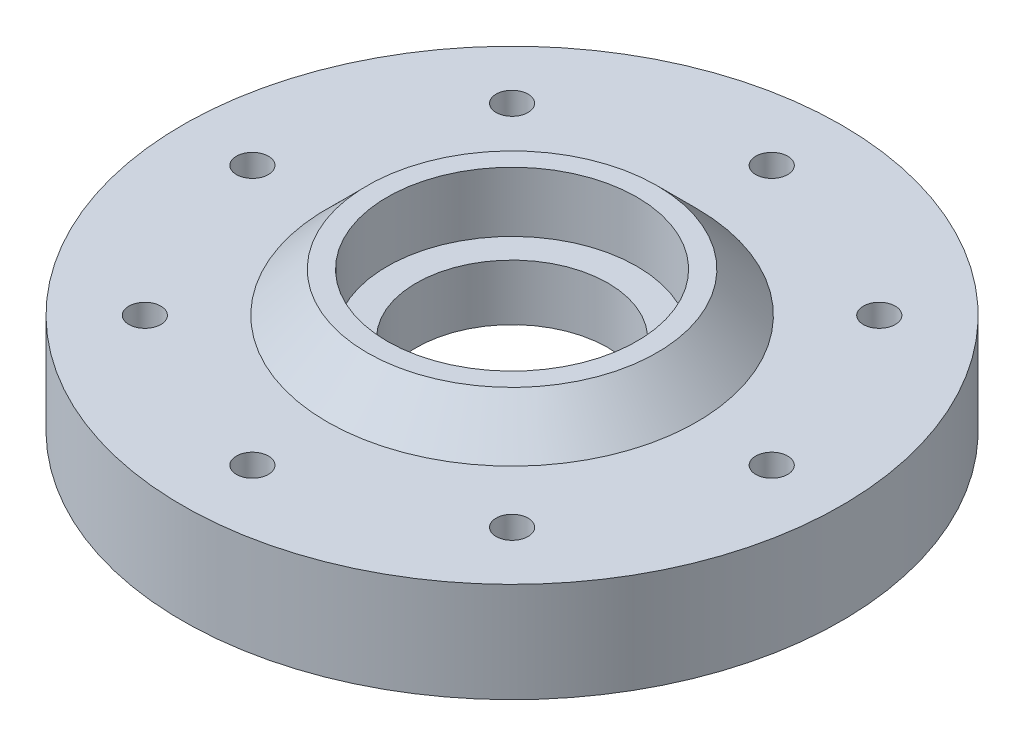
SolidWorks part; units mm, degrees
material "Plain Carbon Steel"
ref_plane "Front Plane" through (0, 0, 0) normal (0, 0, 1) x (1, 0, 0)
ref_plane "Top Plane" through (0, 0, 0) normal (0, 1, 0) x (1, 0, 0)
ref_plane "Right Plane" through (0, 0, 0) normal (1, 0, 0) x (0, 0, -1)
sketch "Sketch1" plane through (0, 0, 0) normal (0, 1, 0) x (1, 0, 0)
  circle A0 centre (0, 0) radius 56 construction
  circle A1 centre (0, 0) radius 82.5 construction
  circle A2 centre (65, 0) radius 4 construction
  circle A3 centre (65, 0) radius 4
  circle A4 centre (45.9619, -45.9619) radius 4 construction
  circle A5 centre (0, -65) radius 4 construction
  circle A6 centre (-45.9619, -45.9619) radius 4 construction
  circle A7 centre (-65, 0) radius 4 construction
  circle A8 centre (-45.9619, 45.9619) radius 4 construction
  circle A9 centre (0, 65) radius 4 construction
  circle A10 centre (45.9619, 45.9619) radius 4 construction
  circle A11 centre (45.9619, -45.9619) radius 4
  circle A12 centre (0, -65) radius 4
  circle A13 centre (-45.9619, -45.9619) radius 4
  circle A14 centre (-65, 0) radius 4
  circle A15 centre (-45.9619, 45.9619) radius 4
  circle A16 centre (0, 65) radius 4
  circle A17 centre (45.9619, 45.9619) radius 4
  circle A18 centre (0, 0) radius 55 construction
  dimension "D1" = 165
  dimension "D2" = 13.5
  dimension "D3" = 1
sketch "Sketch2" plane through (0, 0, 0) normal (0, 0, 1) x (1, 0, 0)
  line L0 (0, 0) -> (0, 67.5538) construction
  line L1 (82.5, 0) -> (56, 0)
  line L2 (82.5, 0) -> (-82.5, 0) construction
  line L3 (56, 0) -> (-56, 0) construction
  line L7 (24, 20) -> (31.2565, 20)
  line L8 (82.5, 25) -> (82.5, 0)
  line L10 (82.5, 25) -> (46.2565, 25)
  line L12 (24, 20) -> (24, 6)
  line L15 (56, 0) -> (56, 6)
  line L16 (56, 6) -> (24, 6)
  line L17 (31.2565, 20) -> (31.2565, 35)
  line L18 (31.2565, 35) -> (36.2565, 35)
  line L19 (36.2565, 35) -> (46.2565, 25)
  point P5 (56, 15)
  point P14 (80.3517, 15)
  point P16 (83.448, 26.7021)
  point P20 (62.1333, 15.9161)
  point P22 (0, 0)
  dimension "D1" = 15
  dimension "D2" = 20
  dimension "D3" = 6
  dimension "D4" = 45
  dimension "D5" = 62.5129
  dimension "D6" = 48
  dimension "D7" = 5
  dimension "D8" = 14
  dimension "D9" = 25
revolve "Revolve1" add sketch "Sketch2" angle 360 about L0
sketch "Sketch3" plane through (0, 0, 0) normal (0, -1, 0) x (1, 0, 0)
  circle A1 centre (65, 0) radius 4
  circle A2 centre (65, 0) radius 4
  circle A3 centre (45.9619, -45.9619) radius 4
  circle A4 centre (45.9619, -45.9619) radius 4
  circle A5 centre (0, -65) radius 4
  circle A6 centre (0, -65) radius 4
  circle A7 centre (-45.9619, -45.9619) radius 4
  circle A8 centre (-45.9619, -45.9619) radius 4
  circle A9 centre (-65, 0) radius 4
  circle A10 centre (-65, 0) radius 4
  circle A11 centre (-45.9619, 45.9619) radius 4
  circle A12 centre (-45.9619, 45.9619) radius 4
  circle A13 centre (0, 65) radius 4
  circle A14 centre (0, 65) radius 4
  circle A15 centre (45.9619, 45.9619) radius 4
  circle A16 centre (45.9619, 45.9619) radius 4
  dimension "D1" = 0
  dimension "D2" = 0
  dimension "D3" = 0
  dimension "D4" = 0
  dimension "D5" = 0
  dimension "D6" = 0
  dimension "D7" = 0
  dimension "D8" = 0
extrude "Cut-Extrude2" cut sketch "Sketch3" against normal through all
